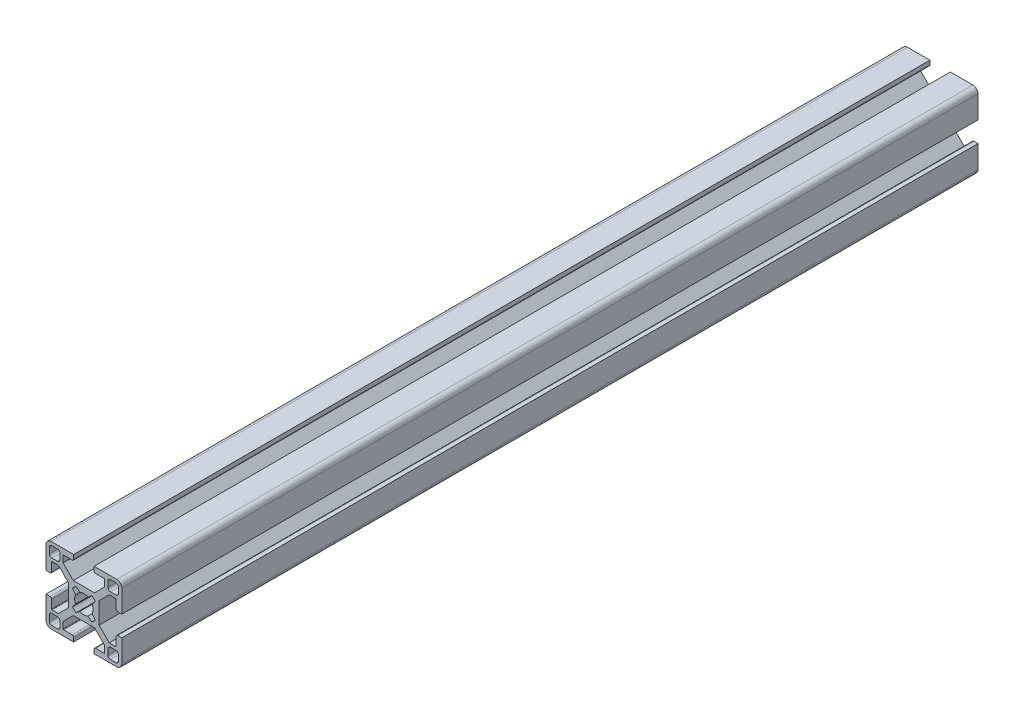
SolidWorks part; units mm, degrees
note: '?' marks a value the reader was unsure of.
other "Title Block Table1"
other "DetailItem1"
material "6082-T6 Aluminium"
ref_plane "Front Plane" through (0, 0, 0) normal (0, 0, 1) x (1, 0, 0)
ref_plane "Top Plane" through (0, 0, 0) normal (0, 1, 0) x (1, 0, 0)
ref_plane "Right Plane" through (0, 0, 0) normal (1, 0, 0) x (0, 0, -1)
ref_axis "X-Axis" through (-55, 0, 0) along (1, 0, 0)?
ref_axis "Y-Axis" through (0, 106.5, 0) along (0, -1, 0)?
ref_axis "Z-Axis" through (0, 0, -15) along (0, 0, 1)?
sketch3d "3DSketch1"
  line L0 (-50, 0, 314) -> (50, 0, 314)
  line L1 (-50, 0, 25) -> (50, 0, 25)
  line L2 (0, 0, 339) -> (0, 0, 0)
  line L3 (0, 0, 100) -> (0, 100, 100)
  line L4 (50, 0, 314) -> (50, 0, 25) construction
  line L5 (-50, 0, 314) -> (-50, 0, 25) construction
  point P7 (0, 0, 314)
  dimension "D1" = 100
  dimension "D6" = 100
  dimension "D2" = 339
  dimension "D3" = 100
  dimension "D4" = 25
  dimension "D5" = 25
other "Bosch rexroth dimension 30 (8mm slots) 30X30(7)" corner treatment miter
ref_plane "Plane1" through (0, 15, 339) normal (0, 0, -1) x (1, 0, 0)
sketch "Sketch1" plane through (0, 15, 339) normal (0, 0, -1) x (1, 0, 0)
  line L0 (13.7, 12.7) -> (13.7, 10.5)
  line L1 (10.5, 9.5) -> (12.7, 9.5)
  line L2 (9.5, 12.7) -> (9.5, 10.5)
  line L3 (10.5, 13.7) -> (12.7, 13.7)
  line L4 (3.1359, 4.5184) -> (1.6001, 3.2806)
  line L5 (3.2806, 1.6001) -> (4.5053, 3.1547)
  line L7 (6.0045, 4.2045) -> (6.0045, -4.2045)
  line L10 (4.2045, -6) -> (8.25, -10.05)
  line L11 (8.25, -10.05) -> (8.25, -12.6)
  line L12 (4.65, -12.8) -> (8.05, -12.8)
  line L13 (4.05, -15) -> (4.05, -13.4)
  line L16 (4.05, -15) -> (13, -15)
  line L17 (15, -13) -> (15, -4.05)
  line L20 (13.4, -4.05) -> (15, -4.05)
  line L21 (12.8, -8.05) -> (12.8, -4.65)
  line L22 (12.6, -8.25) -> (10.05, -8.25)
  line L23 (10.05, -8.25) -> (6.0045, -4.2045)
  line L26 (10.05, 8.25) -> (6.0045, 4.2045)
  line L27 (12.6, 8.25) -> (10.05, 8.25)
  line L28 (12.8, 8.05) -> (12.8, 4.65)
  line L29 (13.4, 4.05) -> (15, 4.05)
  line L32 (15, 13) -> (15, 4.05)
  line L33 (4.05, 15) -> (13, 15)
  line L36 (4.05, 15) -> (4.05, 13.4)
  line L37 (4.65, 12.8) -> (8.05, 12.8)
  line L38 (8.25, 10.05) -> (8.25, 12.6)
  line L39 (4.2045, 6) -> (8.25, 10.05)
  line L42 (-13.7, -12.7) -> (-13.7, -10.5)
  line L43 (-10.5, -9.5) -> (-12.7, -9.5)
  line L44 (-9.5, -12.7) -> (-9.5, -10.5)
  line L45 (-10.5, -13.7) -> (-12.7, -13.7)
  line L46 (-3.1359, -4.5184) -> (-1.6001, -3.2806)
  line L47 (-3.2806, -1.6001) -> (-4.5053, -3.1547)
  line L49 (4.2045, 6) -> (-4.2045, 6)
  line L50 (-4.2045, 6) -> (-8.25, 10.05)
  line L51 (-8.25, 10.05) -> (-8.25, 12.6)
  line L52 (-4.65, 12.8) -> (-8.05, 12.8)
  line L53 (-4.05, 15) -> (-4.05, 13.4)
  line L56 (-4.05, 15) -> (-13, 15)
  line L57 (-15, 13) -> (-15, 4.05)
  line L60 (-13.4, 4.05) -> (-15, 4.05)
  line L61 (-12.8, 8.05) -> (-12.8, 4.65)
  line L62 (-12.6, 8.25) -> (-10.05, 8.25)
  line L63 (-10.05, 8.25) -> (-6.0045, 4.2045)
  line L66 (-10.05, -8.25) -> (-6.0045, -4.2045)
  line L67 (-12.6, -8.25) -> (-10.05, -8.25)
  line L68 (-12.8, -8.05) -> (-12.8, -4.65)
  line L69 (-13.4, -4.05) -> (-15, -4.05)
  line L72 (-15, -13) -> (-15, -4.05)
  line L73 (-4.05, -15) -> (-13, -15)
  line L76 (-4.05, -15) -> (-4.05, -13.4)
  line L77 (3.2806, -1.6001) -> (4.5053, -3.1547)
  line L78 (3.1359, -4.5184) -> (1.6001, -3.2806)
  line L79 (-4.65, -12.8) -> (-8.05, -12.8)
  line L80 (-8.25, -10.05) -> (-8.25, -12.6)
  line L81 (-4.2045, -6) -> (-8.25, -10.05)
  line L82 (4.2045, -6) -> (-4.2045, -6)
  line L84 (10.5, -13.7) -> (12.7, -13.7)
  line L85 (9.5, -12.7) -> (9.5, -10.5)
  line L86 (10.5, -9.5) -> (12.7, -9.5)
  line L87 (13.7, -12.7) -> (13.7, -10.5)
  line L88 (-6.0045, 4.2045) -> (-6.0045, -4.2045)
  line L90 (-3.2806, 1.6001) -> (-4.5053, 3.1547)
  line L91 (-3.1359, 4.5184) -> (-1.6001, 3.2806)
  line L92 (-10.5, 13.7) -> (-12.7, 13.7)
  line L93 (-9.5, 12.7) -> (-9.5, 10.5)
  line L94 (-10.5, 9.5) -> (-12.7, 9.5)
  line L95 (-13.7, 12.7) -> (-13.7, 10.5)
  arc A0 (13.7, 12.7) -> (12.7, 13.7) centre (12.7, 12.7) ccw
  arc A1 (12.7, 9.5) -> (13.7, 10.5) centre (12.7, 10.5) ccw
  arc A2 (9.5, 10.5) -> (10.5, 9.5) centre (10.5, 10.5) ccw
  arc A3 (10.5, 13.7) -> (9.5, 12.7) centre (10.5, 12.7) ccw
  arc A4 (1.6001, 3.2806) -> (-1.6001, 3.2806) centre (0, 0) ccw
  arc A5 (8.25, -12.6) -> (8.05, -12.8) centre (8.05, -12.6) cw
  arc A6 (4.65, -12.8) -> (4.05, -13.4) centre (4.65, -13.4) ccw
  circle A7 centre (0, 0) radius 4 construction
  arc A10 (13, -15) -> (15, -13) centre (13, -13) ccw
  arc A14 (13.4, -4.05) -> (12.8, -4.65) centre (13.4, -4.65) ccw
  arc A15 (12.8, -8.05) -> (12.6, -8.25) centre (12.6, -8.05) cw
  arc A16 (4.5053, 3.1547) -> (3.1359, 4.5184) centre (0, 0) ccw
  arc A17 (12.8, 8.05) -> (12.6, 8.25) centre (12.6, 8.05) ccw
  arc A18 (13.4, 4.05) -> (12.8, 4.65) centre (13.4, 4.65) cw
  arc A22 (13, 15) -> (15, 13) centre (13, 13) cw
  arc A26 (4.65, 12.8) -> (4.05, 13.4) centre (4.65, 13.4) cw
  arc A27 (8.25, 12.6) -> (8.05, 12.8) centre (8.05, 12.6) ccw
  arc A28 (-13.7, -12.7) -> (-12.7, -13.7) centre (-12.7, -12.7) ccw
  arc A29 (-12.7, -9.5) -> (-13.7, -10.5) centre (-12.7, -10.5) ccw
  arc A30 (-9.5, -10.5) -> (-10.5, -9.5) centre (-10.5, -10.5) ccw
  arc A31 (-10.5, -13.7) -> (-9.5, -12.7) centre (-10.5, -12.7) ccw
  arc A32 (-4.5053, -3.1547) -> (-3.1359, -4.5184) centre (0, 0) ccw
  arc A33 (-3.2806, 1.6001) -> (-3.2806, -1.6001) centre (0, 0) ccw
  arc A34 (-8.25, 12.6) -> (-8.05, 12.8) centre (-8.05, 12.6) cw
  arc A35 (-4.65, 12.8) -> (-4.05, 13.4) centre (-4.65, 13.4) ccw
  arc A39 (-13, 15) -> (-15, 13) centre (-13, 13) ccw
  arc A43 (-13.4, 4.05) -> (-12.8, 4.65) centre (-13.4, 4.65) ccw
  arc A44 (-12.8, 8.05) -> (-12.6, 8.25) centre (-12.6, 8.05) cw
  arc A45 (-4.5053, 3.1547) -> (-3.1359, 4.5184) centre (0, 0) cw
  arc A46 (-12.8, -8.05) -> (-12.6, -8.25) centre (-12.6, -8.05) ccw
  arc A47 (-13.4, -4.05) -> (-12.8, -4.65) centre (-13.4, -4.65) cw
  arc A49 (3.2806, 1.6001) -> (3.2806, -1.6001) centre (0, 0) cw
  arc A50 (4.5053, -3.1547) -> (3.1359, -4.5184) centre (0, 0) cw
  arc A51 (1.6001, -3.2806) -> (-1.6001, -3.2806) centre (0, 0) cw
  arc A54 (-13, -15) -> (-15, -13) centre (-13, -13) cw
  arc A56 (10.5, -13.7) -> (9.5, -12.7) centre (10.5, -12.7) cw
  arc A57 (9.5, -10.5) -> (10.5, -9.5) centre (10.5, -10.5) cw
  arc A58 (12.7, -9.5) -> (13.7, -10.5) centre (12.7, -10.5) cw
  arc A59 (13.7, -12.7) -> (12.7, -13.7) centre (12.7, -12.7) cw
  arc A62 (-4.65, -12.8) -> (-4.05, -13.4) centre (-4.65, -13.4) cw
  arc A63 (-8.25, -12.6) -> (-8.05, -12.8) centre (-8.05, -12.6) ccw
  arc A64 (-10.5, 13.7) -> (-9.5, 12.7) centre (-10.5, 12.7) cw
  arc A65 (-9.5, 10.5) -> (-10.5, 9.5) centre (-10.5, 10.5) cw
  arc A66 (-12.7, 9.5) -> (-13.7, 10.5) centre (-12.7, 10.5) cw
  arc A67 (-13.7, 12.7) -> (-12.7, 13.7) centre (-12.7, 12.7) cw
  point P0 (0, 15)
  point P20 (-15, 0)
  point P30 (15, 0)
  point P31 (0, -15)
  point P33 (0, 0)
  point P81 (15, 15)
  point P204 (15, -15)
  point P206 (0, 0)
  point P220 (-15, -15)
  point P221 (-15, 15)
  dimension "Thread" = 8
  dimension "Tap" = 7.3
  dimension "V_leg" = 30
  dimension "H_leg" = 30
  dimension "Slot" = 8.1
